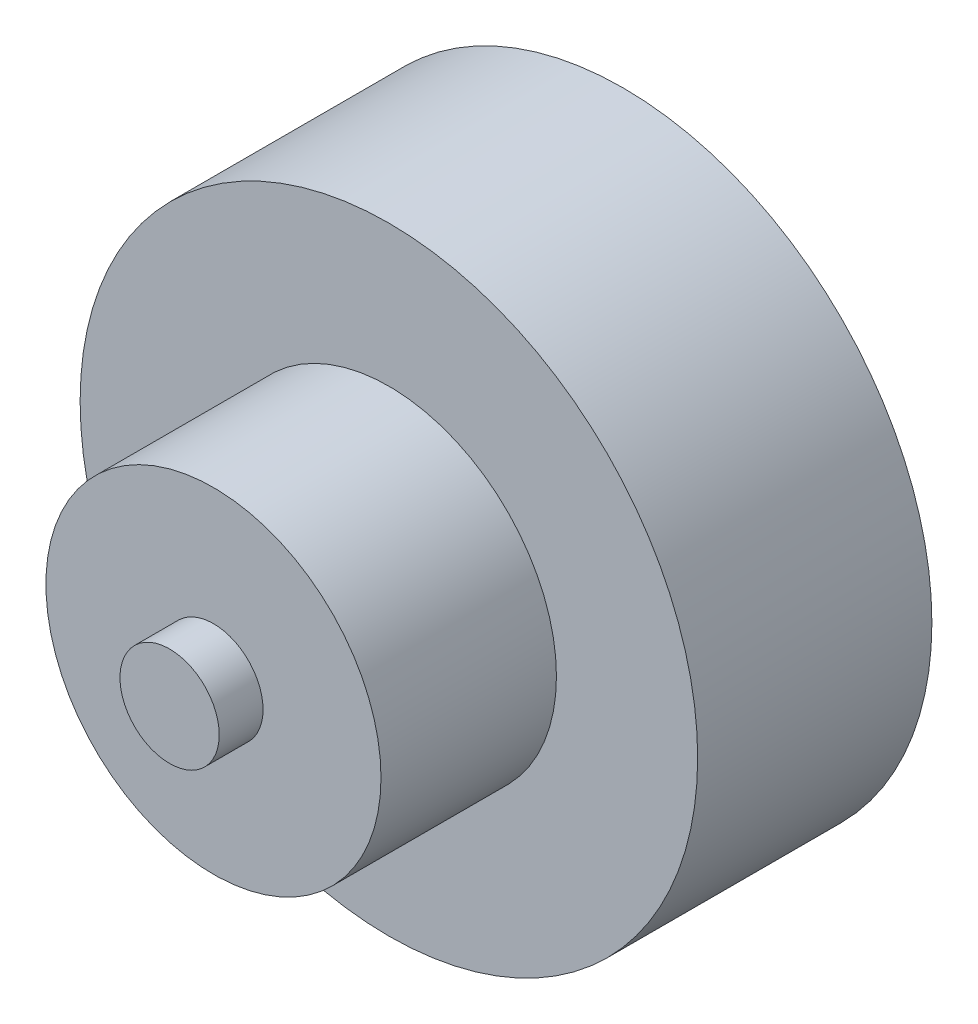
SolidWorks part; units mm, degrees
ref_plane "Front Plane" through (0, 0, 0) normal (0, 0, 1) x (1, 0, 0)
ref_plane "Top Plane" through (0, 0, 0) normal (0, 1, 0) x (1, 0, 0)
ref_plane "Right Plane" through (0, 0, 0) normal (1, 0, 0) x (0, 0, -1)
sketch "Sketch1" plane through (0, 0, 0) normal (1, 0, 0) x (0, 0, -1)
  line L0 (0, 0) -> (-65.659, 0)
  line L1 (0, 0) -> (0, 44.704)
  line L2 (0, 44.704) -> (-33.909, 44.704)
  line L3 (-33.909, 44.704) -> (-33.909, 24.257)
  line L4 (-33.909, 24.257) -> (-59.309, 24.257)
  line L5 (-59.309, 24.257) -> (-59.309, 7.1825)
  line L6 (-59.309, 7.1825) -> (-65.659, 7.1825)
  line L7 (-65.659, 7.1825) -> (-65.659, 0)
  line L8 (0, 0) -> (49.0759, 0) construction
  dimension "D1" = 89.408
  dimension "D2" = 48.514
  dimension "D3" = 25.4
  dimension "D4" = 33.909
  dimension "D5" = 6.35
revolve "Revolve1" add sketch "Sketch1" angle 360 about L8
sketch "Sketch2" plane through (0, 0, 0) normal (1, 0, 0) x (0, 0, -1)
  line L0 (-5.08, 0) -> (121.92, 0) construction
  line L1 (-5.08, 0) -> (248.92, 0)
  arc A0 (248.92, 0) -> (-5.08, 0) centre (121.92, 0) ccw
  point P2 (-5.08, 0)
  dimension "D1" = 254
  dimension "D2" = 5.08
revolve "Cut-Revolve5" cut sketch "Sketch2" angle 360 about L0
ref_axis "Axis1" through (0, 0, 81.3879) along (0, 0, -1)
ref_point "Point1"
